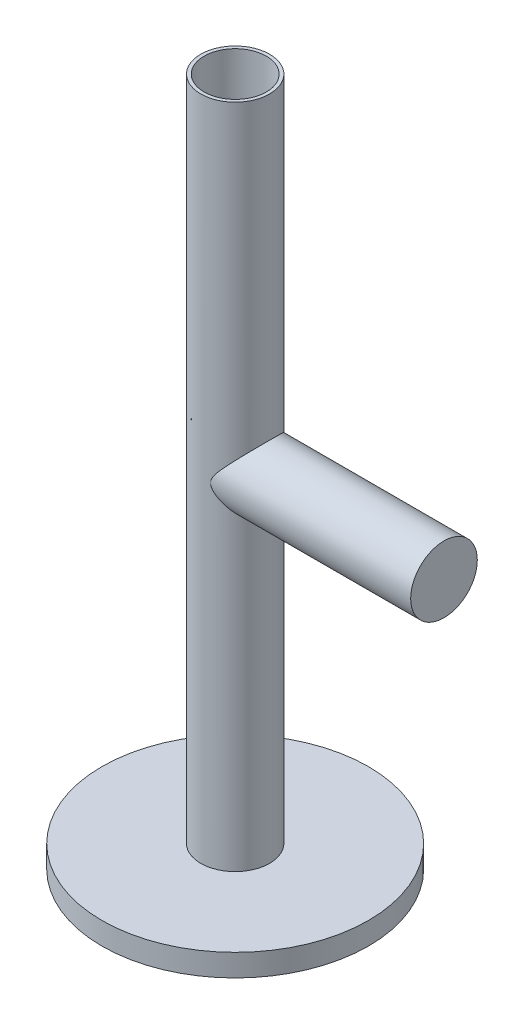
SolidWorks part; units mm, degrees
ref_plane "Front Plane" through (0, 0, 0) normal (0, 0, 1) x (1, 0, 0)
ref_plane "Top Plane" through (0, 0, 0) normal (0, 1, 0) x (1, 0, 0)
ref_plane "Right Plane" through (0, 0, 0) normal (1, 0, 0) x (0, 0, -1)
sketch "Sketch1" plane through (0, 0, 0) normal (0, 1, 0) x (1, 0, 0)
  circle A0 centre (0, 0) radius 7.75
  circle A1 centre (0, 0) radius 7
  dimension "D1" = 15.5
  dimension "D2" = 14
extrude "Boss-Extrude1" add sketch "Sketch1" along normal blind 150
sketch "Sketch2" plane through (0, 0, 0) normal (0, -1, 0) x (1, 0, 0)
  circle A0 centre (0, 0) radius 30
  circle A1 centre (0, 0) radius 9.2467
  dimension "D1" = 60
  dimension "D2" = 18.4935
extrude "Boss-Extrude2" add sketch "Sketch2" along normal blind 5 contours A0
sketch "Sketch5" plane through (0, 0, 0) normal (1, 0, 0) x (0, 0, -1)
  circle A0 centre (0, 75) radius 7.5
  dimension "D1" = 15
extrude "Boss-Extrude3" add sketch "Sketch5" along normal blind 47
sketch "Sketch6" plane through (0, -5, 0) normal (0, -1, 0) x (-1, 0, 0)
  circle A0 centre (0, 0) radius 7
  dimension "D1" = 14
extrude "Cut-Extrude2" cut sketch "Sketch6" against normal blind 170 and the other way blind 10
